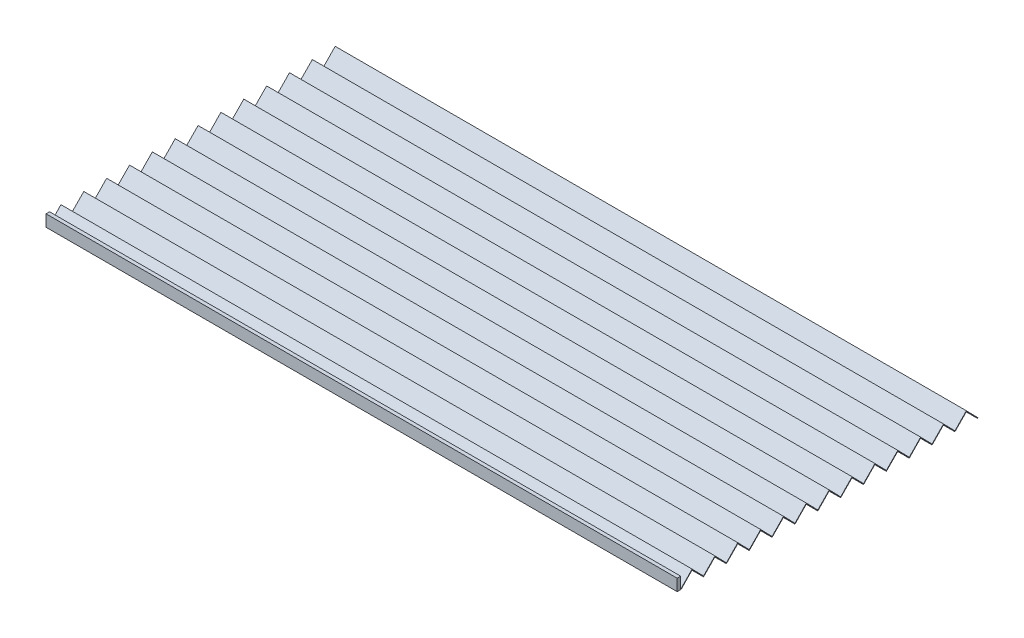
SolidWorks part; units mm, degrees
ref_plane "Front Plane" through (0, 0, 0) normal (0, 0, 1) x (1, 0, 0)
ref_plane "Top Plane" through (0, 0, 0) normal (0, 1, 0) x (1, 0, 0)
ref_plane "Right Plane" through (0, 0, 0) normal (1, 0, 0) x (0, 0, -1)
sketch "Sketch2" plane through (0, 0, 0) normal (0, 0, 1) x (1, 0, 0)
  line L1 (-270, 10) -> (270, 10)
  line L2 (-270, 10) -> (-270, 0)
  line L3 (-270, 0) -> (270, 0)
  line L4 (270, 10) -> (270, 0)
  point P4 (0, 0)
  dimension "D1" = 10
  dimension "D2" = 540
extrude "Boss-Extrude1" add sketch "Sketch2" along normal blind 3
sketch "Sketch3" plane through (270, 0, 0) normal (1, 0, 0) x (0, 0, -1)
  line L0 (0, 10) -> (254.1826, 10) construction
  line L1 (0, 0) -> (254.1826, 0) construction
  line L3 (0, 0) -> (9.7763, 10)
  line L4 (9.7763, 10) -> (19.5525, 0)
  line L5 (19.5525, 0) -> (29.3288, 10)
  line L6 (29.3288, 10) -> (39.105, 0)
  line L7 (39.105, 0) -> (48.8813, 10)
  line L8 (48.8813, 10) -> (58.6575, 0)
  line L9 (58.6575, 0) -> (68.4338, 10)
  line L10 (68.4338, 10) -> (78.21, 0)
  line L11 (78.21, 0) -> (87.9863, 10)
  line L12 (87.9863, 10) -> (97.7625, 0)
  line L13 (97.7625, 0) -> (107.5388, 10)
  line L14 (107.5388, 10) -> (117.3151, 0)
  line L15 (117.3151, 0) -> (127.0913, 10)
  line L16 (127.0913, 10) -> (136.8676, 0)
  line L17 (136.8676, 0) -> (146.6438, 10)
  line L18 (146.6438, 10) -> (156.4201, 0)
  line L20 (156.4201, 0) -> (166.1963, 10)
  line L21 (166.1963, 10) -> (175.9726, 0)
  line L22 (175.9726, 0) -> (185.7488, 10)
  line L23 (185.7488, 10) -> (195.5251, 0)
  line L24 (195.5251, 0) -> (205.3014, 10)
  line L25 (205.3014, 10) -> (215.0776, 0)
  line L26 (215.0776, 0) -> (224.8539, 10)
  line L27 (224.8539, 10) -> (234.6301, 0)
  line L28 (234.6301, 0) -> (244.4064, 10)
  line L29 (244.4064, 10) -> (254.1826, 0)
  line L30 (254.1826, 10) -> (254.1826, 0) construction
  line L32 (254.1826, 10) -> (254.1826, 0) construction
extrude "Extrude-Thin1" add sketch "Sketch3" against normal through all thin thin type mid plane wall 0.5
